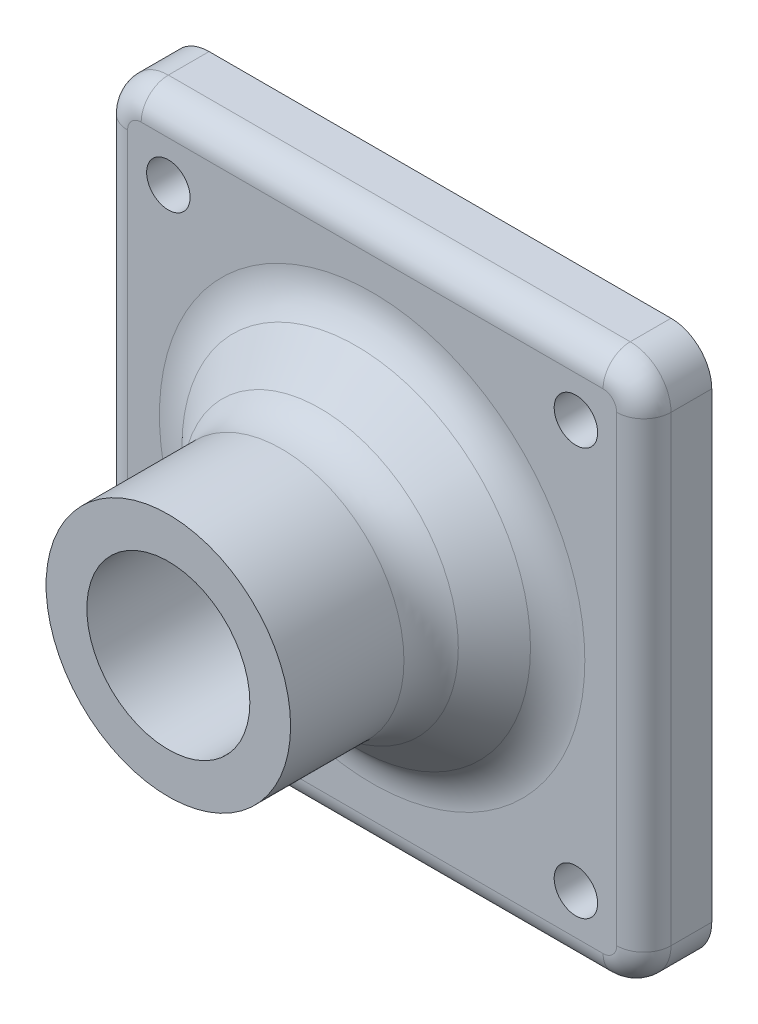
SolidWorks part; units mm, degrees
ref_plane "Front Plane" through (0, 0, 0) normal (0, 0, 1) x (1, 0, 0)
ref_plane "Top Plane" through (0, 0, 0) normal (0, 1, 0) x (1, 0, 0)
ref_plane "Right Plane" through (0, 0, 0) normal (1, 0, 0) x (0, 0, -1)
sketch "Sketch2" plane through (0, 0, 0) normal (0, 0, 1) x (1, 0, 0)
  circle A0 centre (-135, -82.3127) radius 6
  circle A1 centre (-135, -82.3127) radius 9
extrude "Boss-Extrude1" add sketch "Sketch2" along normal blind 20
sketch "Sketch3" plane through (0, 0, 0) normal (0, 0, -1) x (-1, 0, 0)
  line L1 (152, -102.3127) -> (118, -102.3127)
  line L2 (155, -99.3127) -> (155, -65.3127)
  line L3 (152, -62.3127) -> (118, -62.3127)
  line L4 (115, -99.3127) -> (115, -65.3127)
  circle A0 centre (135, -82.3127) radius 6
  arc A5 (118, -102.3127) -> (115, -99.3127) centre (118, -99.3127) cw
  arc A6 (152, -102.3127) -> (155, -99.3127) centre (152, -99.3127) ccw
  arc A7 (155, -65.3127) -> (152, -62.3127) centre (152, -65.3127) ccw
  arc A8 (118, -62.3127) -> (115, -65.3127) centre (118, -65.3127) ccw
  point P8 (115, -102.3127)
  point P11 (155, -102.3127)
  point P14 (155, -62.3127)
  dimension "D1" = 20
  dimension "D5" = 3
  dimension "D2" = 40
  dimension "D3" = 40
  dimension "D4" = 20
extrude "Boss-Extrude2" add sketch "Sketch3" against normal blind 5
fillet "Fillet1" radius 2 8 edges at (-154.1213, -101.434, 5) (-135, -102.3127, 5) (-115.8787, -101.434, 5) (-115, -82.3127, 5) (-115.8787, -63.1913, 5) (-135, -62.3127, 5) (-154.1213, -63.1913, 5) (-155, -82.3127, 5)
sketch "Sketch4" plane through (0, 0, 5) normal (0, 0, 1) x (1, 0, 0)
  line L2 (-135, -62.3127) -> (-135, -102.3127) construction
  line L3 (-152, -62.3127) -> (-118, -62.3127) construction
  line L4 (-118, -102.3127) -> (-152, -102.3127) construction
  line L5 (-155, -82.3127) -> (-115, -82.3127) construction
  line L6 (-155, -99.3127) -> (-155, -65.3127) construction
  line L7 (-115, -65.3127) -> (-115, -99.3127) construction
  circle A0 centre (-150, -67.3127) radius 1.6
  circle A1 centre (-120, -67.3127) radius 1.6
  circle A2 centre (-120, -97.3127) radius 1.6
  circle A3 centre (-150, -97.3127) radius 1.6
extrude "Cut-Extrude1" cut sketch "Sketch4" against normal up to surface (7 mm away)
chamfer "Chamfer1" distance 5 angle 45 1 edges at (-126, -82.3127, 5)
fillet "Fillet2" radius 4 2 edges at (-126, -82.3127, 10) (-121, -82.3127, 5)
